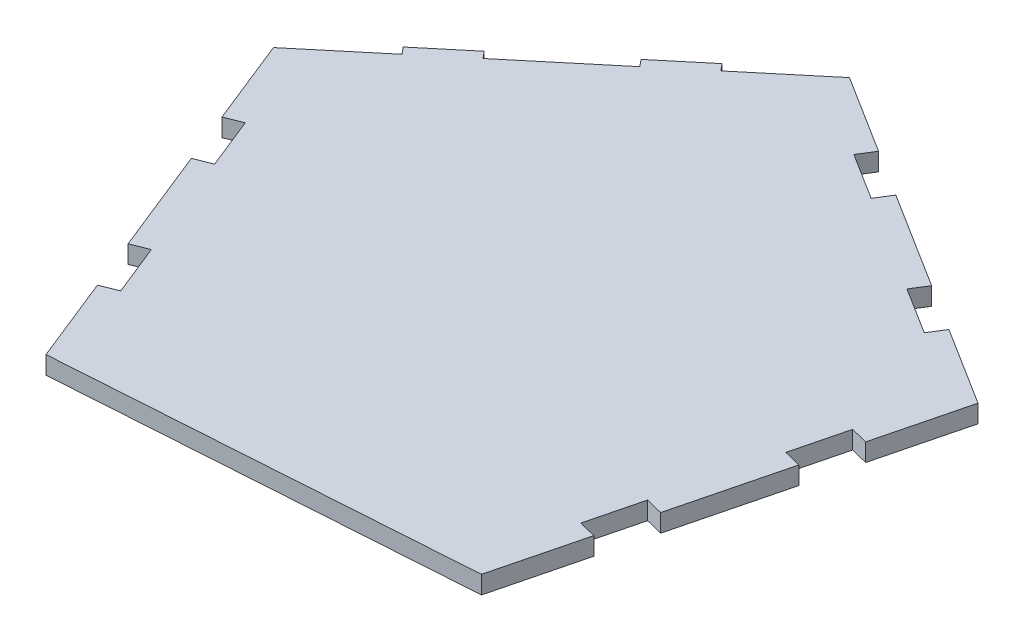
SolidWorks part; units mm, degrees
ref_plane "Front Plane" through (0, 0, 0) normal (0, 0, 1) x (1, 0, 0)
ref_plane "Top Plane" through (0, 0, 0) normal (0, 1, 0) x (1, 0, 0)
ref_plane "Right Plane" through (0, 0, 0) normal (1, 0, 0) x (0, 0, -1)
ref_axis "Axis1" through (0, 3.339, 0) along (0, -1, 0)
sketch "Sketch1" plane through (0, 0, 0) normal (0, 1, 0) x (1, 0, 0)
  line L1 (-59.9258, 15.1181) -> (-32.8962, -52.3211)
  line L2 (-32.8962, -52.3211) -> (39.5948, -47.4543)
  line L3 (39.5948, -47.4543) -> (57.3672, 22.9927)
  line L4 (57.3672, 22.9927) -> (-4.14, 61.6646)
  line L5 (-4.14, 61.6646) -> (-59.9258, 15.1181)
  circle A0 centre (0, 0) radius 50 construction
  dimension "D1" = 100
extrude "Boss-Extrude1" add sketch "Sketch1" along normal blind 3.18
sketch "Sketch2" plane through (0, 0, 0) normal (0, -1, 0) x (1, 0, 0)
  line L0 (-53.8107, 0.1392) -> (-50.859, -1.0438)
  line L1 (-53.8107, 0.1392) -> (-50.1723, 9.2172)
  line L2 (-50.859, -1.0438) -> (-47.2205, 8.0342)
  line L3 (-50.1723, 9.2172) -> (-47.2205, 8.0342)
  line L4 (-59.9258, -15.1181) -> (-32.8962, 52.3211) construction
  line L5 (-42.6498, 27.9858) -> (-39.0113, 37.0638)
  line L6 (-42.6498, 27.9858) -> (-39.6981, 26.8028)
  line L7 (-39.0113, 37.0638) -> (-36.0596, 35.8808)
  line L8 (-39.6981, 26.8028) -> (-36.0596, 35.8808)
  line L9 (-46.411, 18.6015) -> (-19.2439, 7.7129) construction
  line L10 (-40.8306, 32.5248) -> (-37.8788, 31.3418) construction
  dimension "D1" = 3.18
  dimension "D2" = 9.78
  dimension "D3" = 10.11
extrude "Female Cut" cut sketch "Sketch2" against normal through all
sketch "Sketch3" plane through (0, 3.18, 0) normal (0, 1, 0) x (1, 0, 0)
  line L0 (0, 0) -> (-40.9819, 49.1167) construction
  line L1 (-48.4925, 26.7285) -> (-46.4552, 24.2869)
  line L2 (-47.4739, 25.5077) -> (-39.6267, 32.0552)
  line L3 (-46.4552, 24.2869) -> (-38.6081, 30.8344)
  line L4 (-40.6453, 33.2761) -> (-38.6081, 30.8344)
  line L5 (-4.14, 61.6646) -> (-59.9258, 15.1181) construction
  line L6 (-71.9961, 5.0469) -> (-69.9588, 2.6052)
  line L7 (-71.9961, 5.0469) -> (4.7866, 69.1127)
  line L8 (-69.9588, 2.6052) -> (6.8239, 66.671)
  line L9 (4.7866, 69.1127) -> (6.8239, 66.671)
  line L14 (-25.4577, 45.9483) -> (-23.4204, 43.5066)
  line L15 (-24.4391, 44.7274) -> (-16.5919, 51.275)
  line L16 (-23.4204, 43.5066) -> (-15.5733, 50.0541)
  line L17 (-17.6105, 52.4958) -> (-15.5733, 50.0541)
  line L18 (-43.5503, 28.7815) -> (-42.5316, 27.5606) construction
  line L19 (-48.4925, 26.7285) -> (-40.6453, 33.2761)
  line L20 (-7.6874, 54.5631) -> (-9.7247, 57.0048) construction
  line L21 (-25.4577, 45.9483) -> (-17.6105, 52.4958)
  point P19 (0, 0)
  line M18 (-4.14, 61.6646) -> (-59.9258, 15.1181)
  dimension "D1" = 3.18
  dimension "D2" = 10.22
  dimension "D3" = 9.89
  dimension "D4" = 100
pattern_circular "Circle F" [suppressed] count 5 over 360 about axis through (0, 3.339, 0) along (0, -1, 0) of bodies 102
pattern_circular "Circle Side" count 5 over 360 about axis through (0, 3.339, 0) along (0, -1, 0) skipping 1, 4 of "Female Cut"
extrude "Boss-Extrude2" add sketch "Sketch3" against normal up to surface (3.18 mm away) contours L21 L14 L7 L17 | L19 L1 L4 M18 region at (-44.0596, 3.18, -29.3919) region at (-21.0248, 3.18, -48.6116) up to face at (7.6611, 0, -3.0706)
sketch "Sketch5" plane through (0, 3.18, 0) normal (0, 1, 0) x (1, 0, 0)
  line L0 (3.3493, -49.8877) -> (-4.14, 61.6646) construction
  line L1 (-32.8962, -52.3211) -> (39.5948, -47.4543) construction
  line L2 (57.3672, 22.9927) -> (-46.411, -18.6015) construction
  line L3 (-50.1723, -9.2172) -> (-42.6498, -27.9858) construction
  line L4 (-32.0329, 38.3913) -> (39.5948, -47.4543) construction
  line L5 (-24.4391, 44.7274) -> (-39.6267, 32.0552) construction
equation "\"kerf\"= .22mm"
equation "\"tabWidthF\"= 10 - \"kerf\""
equation "\"tabThickness\"= 3.18"
equation "\"D1@Sketch2\"=\"tabThickness\""
equation "\"tabWidthM\"= 10 + \"kerf\""
equation "\"halfkerf\"= \"kerf\" / 2.00mm"
equation "\"tabLength\" = \"kerf\" + 12"
